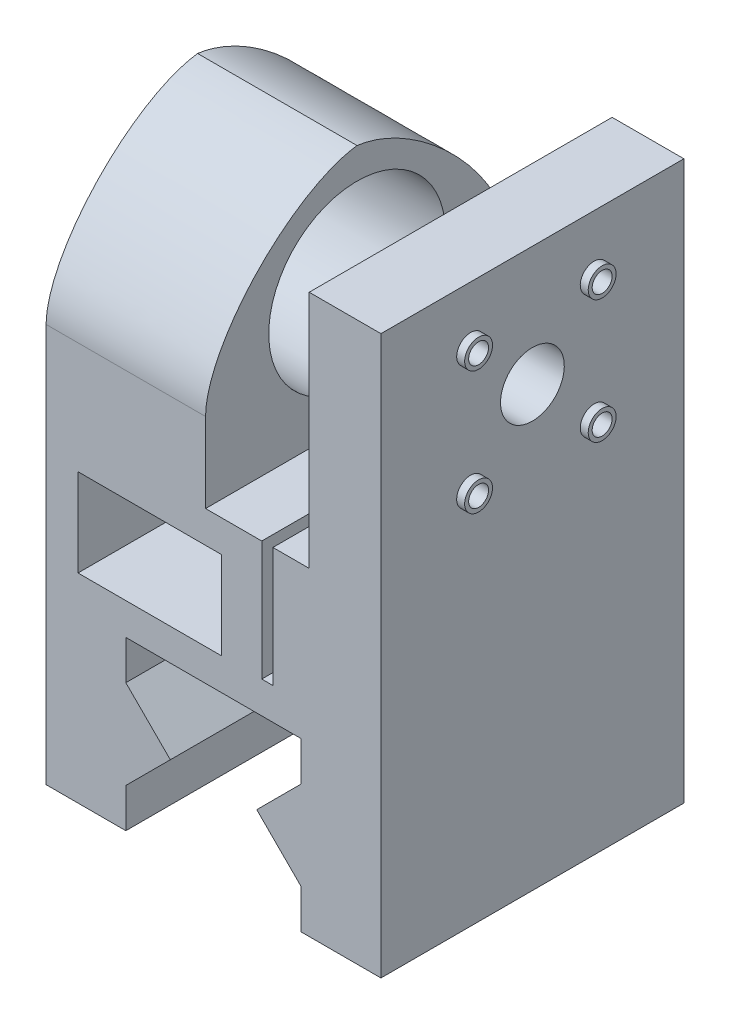
SolidWorks part; units mm, degrees
ref_plane "Front Plane" through (0, 0, 0) normal (0, 0, 1) x (1, 0, 0)
ref_plane "Top Plane" through (0, 0, 0) normal (0, 1, 0) x (1, 0, 0)
ref_plane "Right Plane" through (0, 0, 0) normal (1, 0, 0) x (0, 0, -1)
sketch "Sketch1" plane through (0, 0, 0) normal (0, 0, 1) x (1, 0, 0)
  line L0 (-11, 0) -> (11, 0)
  line L1 (11, 0) -> (11, -4.92)
  line L2 (11, -4.92) -> (5.42, -10.5)
  line L3 (5.42, -10.5) -> (11, -10.5) construction
  line L4 (11, -16.08) -> (5.42, -10.5)
  line L5 (11, -16.08) -> (11, -21)
  line L6 (0, 0) -> (0, -50000) construction
  line L7 (11, -21) -> (21, -21)
  line L8 (21, -21) -> (21, 19)
  line L9 (21, 19) -> (-21, 19)
  line L10 (-5.42, -10.5) -> (-11, -10.5) construction
  line L11 (-21, -21) -> (-21, 19)
  line L12 (-11, -21) -> (-21, -21)
  line L13 (-11, -16.08) -> (-11, -21)
  line L14 (-11, -16.08) -> (-5.42, -10.5)
  line L15 (-11, -4.92) -> (-5.42, -10.5)
  line L16 (-11, 0) -> (-11, -4.92)
  line L18 (-17, 15) -> (1, 15)
  line L19 (-17, 15) -> (-17, 4)
  line L20 (-17, 4) -> (1, 4)
  line L21 (1, 15) -> (1, 4)
  point P16 (0, 19)
  point P21 (0, 0)
  dimension "D1" = 11
  dimension "D2" = 4.92
  dimension "D3" = 7.8913
  dimension "D4" = 45
  dimension "D5" = 4.92
  dimension "D6" = 10
  dimension "D7" = 40
  dimension "D8" = 4
  dimension "D9" = 4
  dimension "D10" = 20
  dimension "D11" = 4
extrude "Boss-Extrude1" add sketch "Sketch1" along normal mid plane 38
sketch "Sketch2" plane through (0, 19, 0) normal (0, 1, 0) x (1, 0, 0)
  line L0 (21, -19) -> (-21, -19) construction
  line L1 (-21, 19) -> (-1, 19)
  line L2 (-21, 19) -> (-21, -19)
  line L3 (-21, -19) -> (-1, -19)
  line L4 (-1, 19) -> (-1, -19)
  dimension "D1" = 20
extrude "Boss-Extrude2" add sketch "Sketch2" along normal blind 30
fillet "Fillet2" radius 20 2 edges at (-11, 49, -19) (-11, 49, 19) conic rho 0.3
sketch "Sketch7" plane through (0, 19, 0) normal (0, 1, 0) x (1, 0, 0)
  line L0 (21, 19) -> (-1, 19) construction
  line L1 (12, 19) -> (21, 19)
  line L2 (12, 19) -> (12, -19)
  line L3 (12, -19) -> (21, -19)
  line L4 (21, 19) -> (21, -19)
  dimension "D1" = 9
extrude "Boss-Extrude6" add sketch "Sketch7" along normal blind 30
sketch "Sketch3" plane through (-21, 0, 0) normal (-1, 0, 0) x (0, 0, 1)
  line L0 (0, 0) -> (0, 44) construction
  circle A0 centre (0, 34) radius 11.075
  dimension "D1" = 22.15
  dimension "D2" = 34
extrude "Cut-Extrude1" cut sketch "Sketch3" against normal blind 31 and the other way through all
sketch "Sketch9" plane through (21, 0, 0) normal (1, 0, 0) x (0, 0, -1)
  line L0 (-19, 49) -> (19, 49) construction
  line L1 (-19, -21) -> (-19, 49) construction
  line L2 (19, -21) -> (19, 49) construction
  circle A0 centre (-7.75, 41.75) radius 1.75
  circle A1 centre (7.75, 41.75) radius 1.75
  circle A2 centre (-7.75, 26.25) radius 1.75
  circle A3 centre (7.75, 26.25) radius 1.75
  point P0 (-7.75, 41.75)
  point P2 (7.75, 41.75)
  point P4 (-7.75, 26.25)
  point P7 (7.75, 26.25)
  dimension "D1" = 3.5
  dimension "D2" = 3.5
  dimension "D3" = 3.5
  dimension "D4" = 3.5
  dimension "D5" = 7.25
  dimension "D6" = 11.25
  dimension "D7" = 11.25
  dimension "D8" = 15.5
ref_axis "Axis1" through (-1, 34, 0) along (-1, 0, 0)
sketch "Sketch5" plane through (0, 19, 0) normal (0, 1, 0) x (1, 0, 0)
  line L0 (12, 19) -> (-1, 19) construction
  line L1 (18.5, 19) -> (21, 19)
  line L2 (18.5, 19) -> (18.5, -19)
  line L3 (18.5, -19) -> (21, -19)
  line L4 (21, 19) -> (21, -19)
  line L5 (12, -19) -> (-1, -19) construction
  line L6 (21, -19) -> (21, 19) construction
  dimension "D1" = 2.5
extrude "Boss-Extrude3" add sketch "Sketch5" along normal blind 30
sketch "Sketch8" plane through (21, 0, 0) normal (1, 0, 0) x (0, 0, -1)
  line L0 (-19, 49) -> (19, 49) construction
  circle A0 centre (0, 34) radius 4
  dimension "D1" = 15
  dimension "D2" = 8
extrude "Cut-Extrude4" cut sketch "Sketch8" against normal through all
sketch "Sketch11" plane through (0, 19, 0) normal (0, 1, 0) x (1, 0, 0)
  line L0 (0, 0) -> (21, 0) construction
  line L1 (21, -19) -> (21, 19) construction
  line L2 (6.75, 19) -> (6.75, -19) construction
  line L3 (6.05, -10.8497) -> (6.05, -19)
  line L4 (7.45, -10.8497) -> (7.45, -19)
  line L5 (6.05, 19) -> (6.05, 10.8497)
  line L6 (7.45, 19) -> (7.45, 10.8497)
  line L7 (6.05, 19) -> (7.45, 19)
  line L8 (6.05, -19) -> (7.45, -19)
  line L9 (7.45, 1.1503) -> (7.45, -1.1503)
  line L10 (6.05, 1.1503) -> (6.05, -1.1503)
  circle A0 centre (6.75, 6) radius 3.5
  circle A1 centre (6.75, -6) radius 3.5
  arc A2 (7.45, 1.1503) -> (7.45, 10.8497) centre (6.75, 6) ccw
  arc A3 (7.45, -10.8497) -> (7.45, -1.1503) centre (6.75, -6) ccw
  arc A4 (6.05, -1.1503) -> (6.05, -10.8497) centre (6.75, -6) ccw
  arc A5 (6.05, 10.8497) -> (6.05, 1.1503) centre (6.75, 6) ccw
  dimension "D7" = 7
  dimension "D8" = 9.8
  dimension "D9" = 9.8
  dimension "D1" = 38
  dimension "D2" = 1.4
  dimension "D3" = 6.05
  dimension "D4" = 19
  dimension "D5" = 6
  dimension "D6" = 6
extrude "Cut-Extrude5" cut sketch "Sketch11" against normal blind 15
sketch "Sketch16" plane through (0, 19, 0) normal (0, 1, 0) x (1, 0, 0)
  line L0 (6.05, 1.1503) -> (6.05, -1.1503)
  line L1 (7.45, -1.1503) -> (7.45, 1.1503)
  arc A0 (6.05, 1.1503) -> (7.45, 1.1503) centre (6.75, 6) ccw
  arc A1 (7.45, -1.1503) -> (6.05, -1.1503) centre (6.75, -6.5047) ccw
  dimension "D2" = 10.8
extrude "Boss-Extrude8" add sketch "Sketch16" against normal blind 15
extrude "Boss-Extrude7" add sketch "Sketch9" along normal blind 1
hole_wizard "Tap Drill for M3x0.5 Tap2" positions "3DSketch2" profile "Sketch15" hole size "M3x0.5" standard "ANSI Metric"
sketch3d "3DSketch2"
  line L0 (22, 41.75, 7.75) -> (21, 41.75, 7.75) construction
  line L1 (22, 41.75, -7.75) -> (21, 41.75, -7.75) construction
  line L2 (22, 26.25, -7.75) -> (21, 26.25, -7.75) construction
  line L3 (22, 26.25, 7.75) -> (21, 26.25, 7.75) construction
  point P0 (22, 41.75, 7.75)
  point P4 (-56.5655, 53.6952, 0)
  point P6 (-52.3499, 57.5798, 0)
  point P8 (22, 41.75, -7.75)
  point P12 (-34.3171, 58.8554, 0)
  point P14 (22, 26.25, -7.75)
  point P18 (22, 26.25, 7.75)
sketch "Sketch15" plane through (22, 41.75, 7.75) normal (0, 1, 0) x (0, 0, -1)
  line L0 (0, 0) -> (0, 8)
  line L1 (0, 8) -> (1.25, 8)
  line L2 (1.25, 8) -> (1.25, 0)
  line L5 (1.25, 0) -> (0, 0)
  line L10 (0, 8) -> (-1.25, 8) construction
  line L11 (0, -6.35) -> (0, 107.95) construction
  dimension "Hole Dia." = 2.5
  dimension "Hole Depth" = 8
  dimension "Drill Angle" = 180
